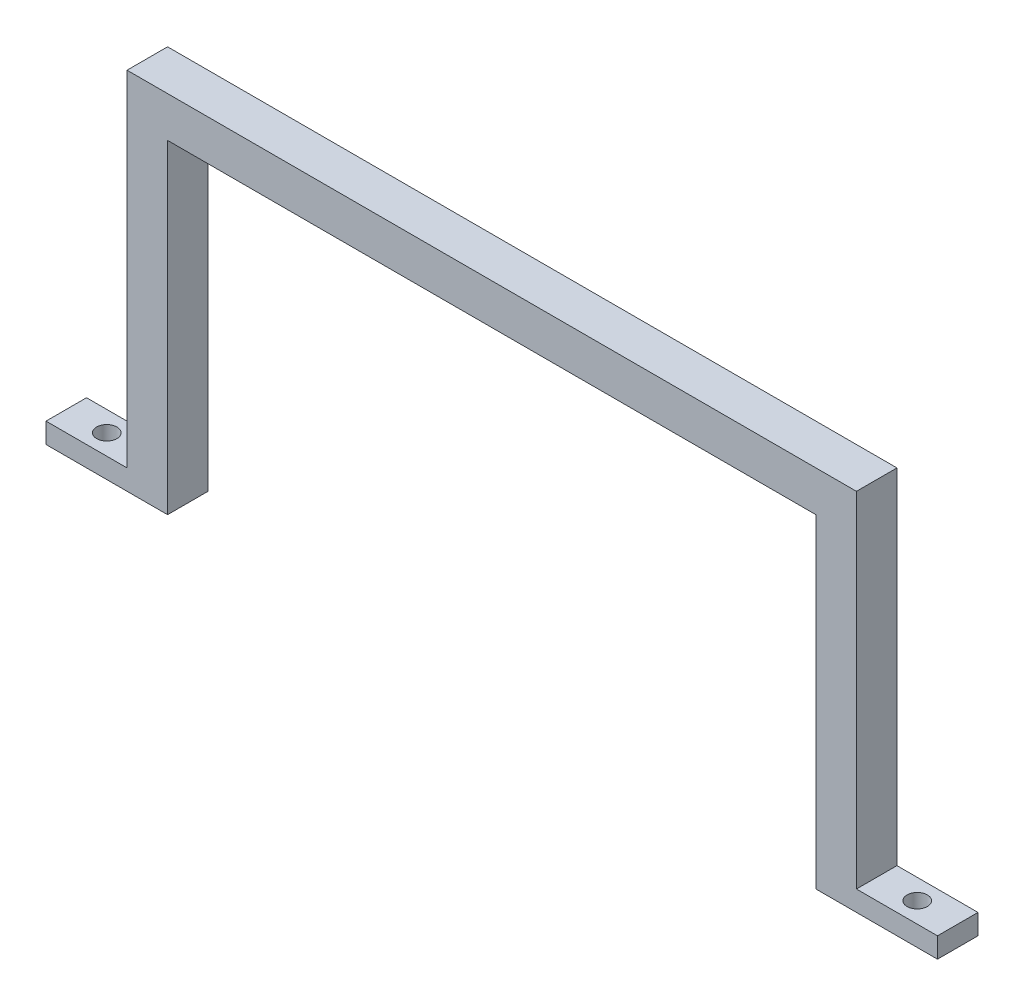
SolidWorks part; units mm, degrees
ref_plane "Front Plane" through (0, 0, 0) normal (0, 0, 1) x (1, 0, 0)
ref_plane "Top Plane" through (0, 0, 0) normal (0, 1, 0) x (1, 0, 0)
ref_plane "Right Plane" through (0, 0, 0) normal (1, 0, 0) x (0, 0, -1)
sketch "Sketch1" plane through (0, 0, 0) normal (0, 1, 0) x (1, 0, 0)
  line L1 (-57.15, 3.175) -> (57.15, 3.175)
  line L2 (-57.15, 3.175) -> (-57.15, -3.175)
  line L3 (-57.15, -3.175) -> (57.15, -3.175)
  line L4 (57.15, 3.175) -> (57.15, -3.175)
  line L5 (-57.15, 3.175) -> (57.15, -3.175) construction
  line L6 (-57.15, -3.175) -> (57.15, 3.175) construction
  point P0 (0, 0)
  dimension "D1" = 6.35
  dimension "D2" = 114.3
extrude "Boss-Extrude1" add sketch "Sketch1" along normal blind 6.35
sketch "Sketch2" plane through (0, 0, 0) normal (0, -1, 0) x (1, 0, 0)
  line L0 (57.15, -3.175) -> (-57.15, -3.175) construction
  line L1 (-57.15, 3.175) -> (-50.8, 3.175)
  line L2 (-57.15, 3.175) -> (-57.15, -3.175)
  line L3 (-57.15, -3.175) -> (-50.8, -3.175)
  line L4 (-50.8, 3.175) -> (-50.8, -3.175)
  dimension "D1" = 6.35
extrude "Boss-Extrude2" add sketch "Sketch2" along normal blind 50.8
sketch "Sketch3" plane through (-57.15, 0, 0) normal (-1, 0, 0) x (0, 0, 1)
  line L0 (3.175, 6.35) -> (3.175, -50.8) construction
  line L1 (-3.175, -50.8) -> (3.175, -50.8)
  line L2 (-3.175, -50.8) -> (-3.175, -47.625)
  line L3 (-3.175, -47.625) -> (3.175, -47.625)
  line L4 (3.175, -50.8) -> (3.175, -47.625)
  dimension "D1" = 3.175
extrude "Boss-Extrude3" add sketch "Sketch3" along normal blind 12.7
mirror "Mirror1" about plane through (0, 0, 0) normal (1, 0, 0) of "Boss-Extrude3", "Boss-Extrude2"
sketch "Sketch4" plane through (0, -47.625, 0) normal (0, 1, 0) x (1, 0, 0)
  line L0 (-69.85, 3.175) -> (-57.15, 3.175) construction
  line L1 (-69.85, -3.175) -> (-69.85, 3.175) construction
  circle A0 centre (-63.5, 0) radius 1.5875
  dimension "D1" = 3.175
  dimension "D3" = 6.35
  dimension "D2" = 3.175
extrude "Cut-Extrude1" cut sketch "Sketch4" against normal up to next
mirror "Mirror2" about plane through (0, 0, 0) normal (1, 0, 0) of "Cut-Extrude1"
